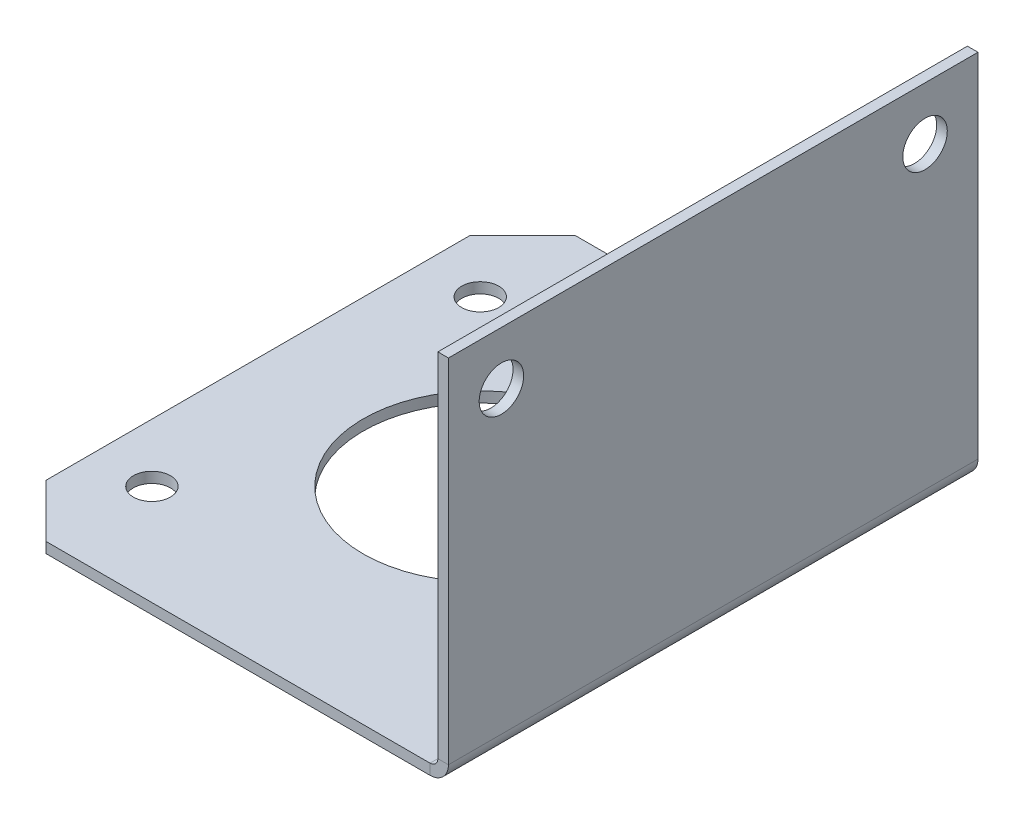
SolidWorks part; units mm, degrees
note: The reader was unsure of these and kept them because the rebuilt part matched: thickness of "Base-Flange1", "Edge-Flange1", "Sheet-Metal1", "Sheet-Metal2", "Sheet-Metal8", "Sheet-Metal9"; flange length of "Edge-Flange1".
material "1060 Alloy"
ref_plane "Front Plane" through (0, 0, 0) normal (0, 0, 1) x (1, 0, 0)
ref_plane "Top Plane" through (0, 0, 0) normal (0, 1, 0) x (1, 0, 0)
ref_plane "Right Plane" through (0, 0, 0) normal (1, 0, 0) x (0, 0, -1)
sketch "Sketch1" plane through (0, 0, 0) normal (0, 1, 0) x (1, 0, 0)
  line L1 (0, -25) -> (43, -25)
  line L2 (0, -25) -> (0, 25)
  line L3 (0, 25) -> (43, 25)
  line L4 (43, -25) -> (43, 25)
  point P7 (0, 0)
  dimension "D1" = 43
  dimension "D2" = 50
base flange "Base-Flange1" sketch "Sketch1" thickness 1 reverse thickness direction no parameters "D1"=0.7366
sketch "Sketch2" plane through (0, 0, 0) normal (0, 1, 0) x (1, 0, 0)
  line L0 (0, 25) -> (0, -25) construction
  line L2 (5.5, 15.5) -> (36.5, 15.5) construction
  line L3 (5.5, 15.5) -> (5.5, -15.5) construction
  line L4 (5.5, -15.5) -> (36.5, -15.5) construction
  line L5 (36.5, 15.5) -> (36.5, -15.5) construction
  circle A0 centre (21, 0) radius 11.05
  circle A1 centre (5.5, 15.5) radius 1.75
  circle A2 centre (36.5, 15.5) radius 1.75
  circle A3 centre (36.5, -15.5) radius 1.75
  circle A4 centre (5.5, -15.5) radius 1.75
  point P2 (36.5, 0)
  point P5 (0, 0)
  point P10 (5.5, 0)
  point P11 (21, 15.5)
  dimension "D1" = 22.1
  dimension "D2" = 21
  dimension "D4" = 3.5
  dimension "D3" = 31
extrude "Cut-Extrude1" cut sketch "Sketch2" against normal through all
edge flange "Edge-Flange1" sketch "Sketch7" flange angle 90 flange length 35 flange position material inside bend radius 0.7366 thickness 1 relief rectangular parameters "D6"=10
sketch "Sketch7" plane through (43, 0, 0) normal (1, 0, 0) x (0, 0, -1)
  line L0 (-25, 0) -> (25, 0) construction
  line L1 (-25, 0) -> (25, 0)
  line L2 (-25, 0) -> (-25, 34)
  line L3 (-25, 34) -> (25, 34)
  line L4 (25, 34) -> (25, 0)
bend "EdgeBend1" bend radius 0.7366 bend angle 90 parameters "D5"=1
sketch "Sketch8" plane through (42, 0, 0) normal (-1, 0, 0) x (0, 0, 1)
  line L0 (0, -12.9764) -> (0, 59.7655) construction
  line L1 (-25, 34) -> (25, 34) construction
  circle A0 centre (20, 29) radius 2.1
  circle A1 centre (-20, 29) radius 2.1
  dimension "D2" = 4.2
  dimension "D1" = 40
  dimension "D3" = 5
extrude "Cut-Extrude2" cut sketch "Sketch8" against normal up to next normal cut yes
chamfer "Chamfer1" distance 5 angle 45 2 edges at (0, -0.5, -25) (0, -0.5, 25)
sketch "Bend-Lines1" [suppressed] plane through (0, 0, 0) normal (0, 1, 0) x (1, 0, 0)
sketch "Bounding-Box1" [suppressed] plane through (0, 0, 0) normal (0, 1, 0) x (1, 0, 0)
sheet metal parameters "Sheet-Metal1" thickness 1 parameters "D1"=0.7366
flat pattern "Flat-Pattern1" [suppressed]
sketch "Bend-Lines2" plane through (0, 0, 0) normal (0, 1, 0) x (1, 0, 0)
  point P0 (49, 50)
  point P1 (49, 0)
sketch3d "Bounding-Box2" [suppressed]
  line L0 (100, 50, 0) -> (0, 50, 0) construction
  line L1 (100, 0, 0) -> (0, 0, 0) construction
  line L2 (100, 50, 0) -> (100, 0, 0) construction
  line L3 (0, 50, 0) -> (0, 0, 0) construction
sheet metal parameters "Sheet-Metal2" thickness 1 parameters "D1"=0.7366, "D7"=3
flat pattern "Flat-Pattern1"
sketch "Bend-Lines2" plane through (0, 0, 0) normal (0, 1, 0) x (1, 0, 0)
sketch3d "Bounding-Box2" [suppressed]
  line L0 (0, -25, 0) -> (0, 25, 0) construction
  line L1 (44, -25, 0) -> (44, 25, 0) construction
  line L2 (0, -25, 0) -> (44, -25, 0) construction
  line L3 (0, 25, 0) -> (44, 25, 0) construction
sheet metal parameters "Sheet-Metal8" thickness 1 parameters "D1"=0.7366, "D7"=3
flat pattern "Flat-Pattern1"
sketch "Bend-Lines2" plane through (0, 0, 0) normal (0, 1, 0) x (1, 0, 0)
  line L0 (42.2346, -25) -> (42.2346, 25) construction
  line L1 (42.2346, -25) -> (42.2346, 25) construction
sketch3d "Bounding-Box2" [suppressed]
  line L0 (71.4692, 25, 0) -> (0, 25, 0) construction
  line L1 (71.4692, -25, 0) -> (0, -25, 0) construction
  line L2 (71.4692, 25, 0) -> (71.4692, -25, 0) construction
  line L3 (0, 25, 0) -> (0, -25, 0) construction
bend of the flat pattern "Flatten-<EdgeBend1>1"
sheet metal parameters "Sheet-Metal9" thickness 1 parameters "D1"=0.7366, "D7"=3
flat pattern "Flat-Pattern1"
sketch "Bend-Lines2" plane through (0, 0, 0) normal (0, 1, 0) x (1, 0, 0)
  line L0 (42.2346, -25) -> (42.2346, 25) construction
  line L1 (42.2346, -25) -> (42.2346, 25) construction
sketch3d "Bounding-Box2" [suppressed]
  line L0 (76.4692, 25, 0) -> (0, 25, 0) construction
  line L1 (76.4692, -25, 0) -> (0, -25, 0) construction
  line L2 (76.4692, 25, 0) -> (76.4692, -25, 0) construction
  line L3 (0, 25, 0) -> (0, -25, 0) construction
bend of the flat pattern "Flatten-<EdgeBend1>1"
